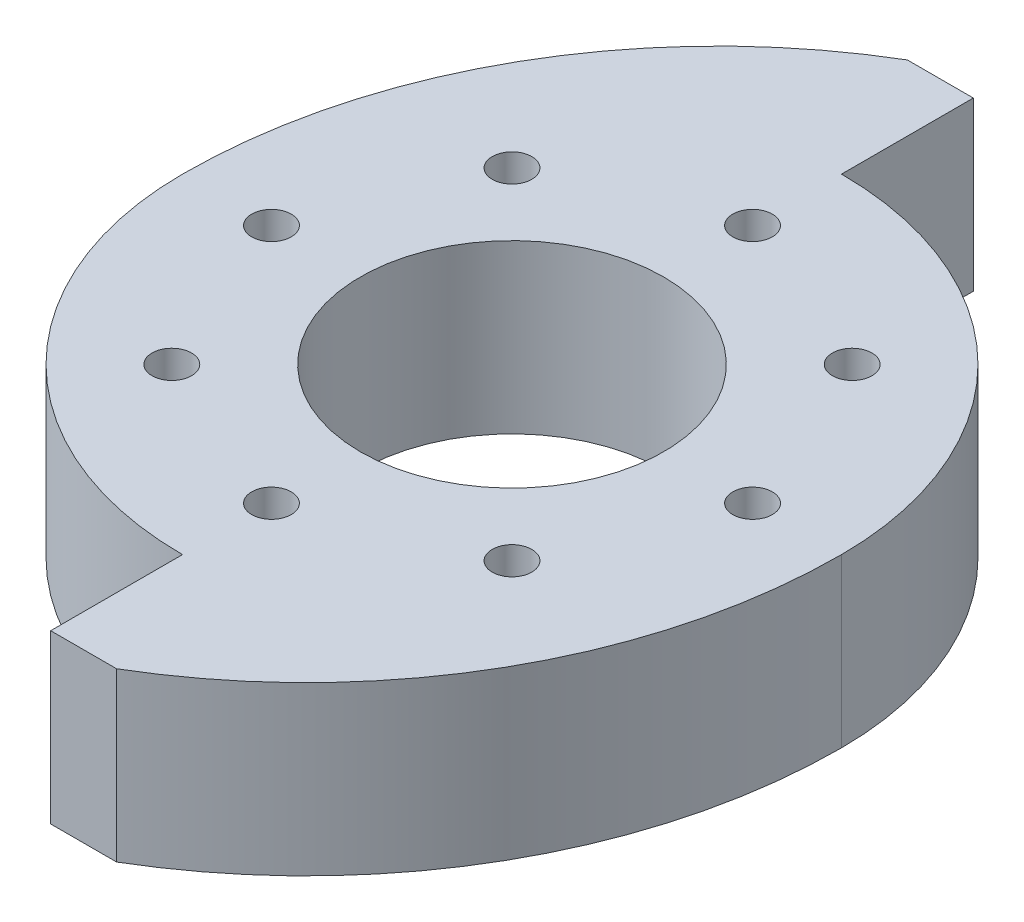
SolidWorks part; units mm, degrees
material "Plain Carbon Steel"
ref_plane "Front Plane" through (0, 0, 0) normal (0, 0, 1) x (1, 0, 0)
ref_plane "Top Plane" through (0, 0, 0) normal (0, 1, 0) x (1, 0, 0)
ref_plane "Right Plane" through (0, 0, 0) normal (1, 0, 0) x (0, 0, -1)
ref_axis "X" through (-88.99, 0, 0) along (1, 0, 0)
ref_axis "Y" through (0, 55, 0) along (0, -1, 0)
ref_axis "Z" through (0, 0, -88.99) along (0, 0, 1)
sketch "Sketch1" plane through (0, 0, 0) normal (0, 1, 0) x (1, 0, 0)
  line L0 (0, 25) -> (0, 35)
  line L1 (0, 35) -> (-5, 35)
  line L2 (0, -25) -> (0, -35)
  line L3 (0, -35) -> (5, -35)
  line L4 (0, 11.5) -> (0, 25) construction
  circle A0 centre (0, 0) radius 25
  arc A1 (-5, 35) -> (-25, 0) centre (15.625, 0) ccw
  arc A2 (5, -35) -> (25, 0) centre (-15.625, 0) ccw
  circle A3 centre (0, 0) radius 11.5
  circle A4 centre (0, 18.25) radius 1.5
  circle A5 centre (12.9047, 12.9047) radius 1.5
  circle A6 centre (18.25, 0) radius 1.5
  circle A7 centre (12.9047, -12.9047) radius 1.5
  circle A8 centre (0, -18.25) radius 1.5
  circle A9 centre (-12.9047, -12.9047) radius 1.5
  circle A10 centre (-18.25, 0) radius 1.5
  circle A11 centre (-12.9047, 12.9047) radius 1.5
  point P16 (0, 0)
  point P18 (20.6049, -4.9942)
  point P19 (0, 0)
  point P35 (0, 0)
  dimension "D1" = 50
  dimension "D4" = 2
  dimension "D5" = 23
  dimension "D6" = 3
  dimension "D2" = 10
  dimension "D3" = 5
  dimension "D7" = 8
extrude "Boss-Extrude1" add sketch "Sketch1" along normal mid plane 12.7 contours A0 A3 | L1 A1 A0 L0 | L3 A2 A0 L2 region at (-9.8514, 0, -25.8127) region at (17.1777, 0, -17.1777) region at (9.8514, 0, 25.8127)
